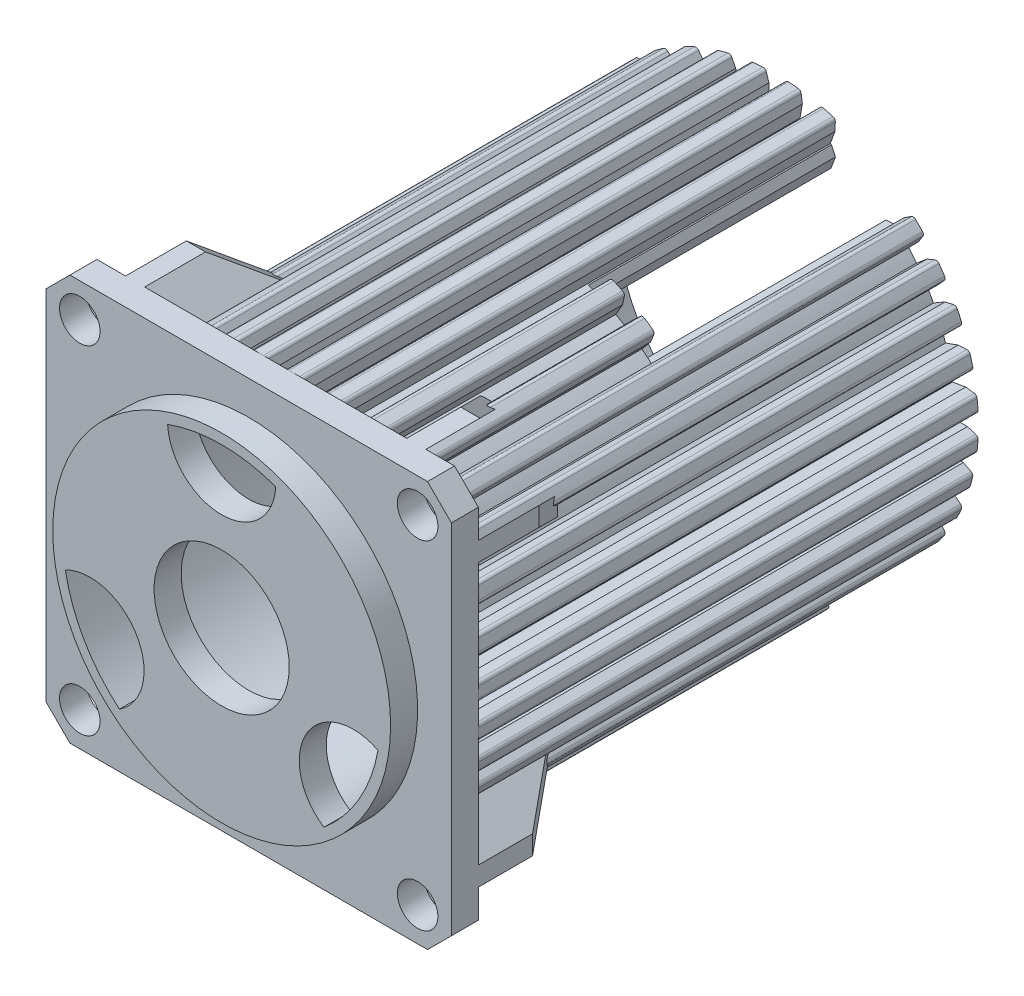
SolidWorks part; units mm, degrees
ref_plane "Alzado" through (0, 0, 0) normal (0, 0, 1) x (1, 0, 0)
ref_plane "Planta" through (0, 0, 0) normal (0, 1, 0) x (1, 0, 0)
ref_plane "Vista lateral" through (0, 0, 0) normal (1, 0, 0) x (0, 0, -1)
sketch "Croquis1" plane through (0, 0, 0) normal (0, 0, 1) x (1, 0, 0)
  line L1 (-15, -15) -> (15, -15)
  line L2 (-15, -15) -> (-15, 15)
  line L3 (-15, 15) -> (15, 15)
  line L4 (15, -15) -> (15, 15)
  line L5 (-15, -15) -> (15, 15) construction
  line L6 (-15, 15) -> (15, -15) construction
  circle A0 centre (0, 0) radius 11.75
  circle A1 centre (-12.5, 12.5) radius 1.5
  circle A2 centre (-12.5, -12.5) radius 1.5
  circle A3 centre (12.5, -12.5) radius 1.5
  circle A4 centre (12.5, 12.5) radius 1.5
  dimension "D1" = 23.5
  dimension "D3" = 3
  dimension "D4" = 25
  dimension "D2" = 30
extrude "Saliente-Extruir1" add sketch "Croquis1" against normal blind 2
sketch "Croquis2" plane through (0, 0, 0) normal (0, 0, 1) x (1, 0, 0)
  line L0 (-15, -15) -> (15, 15) construction
  circle A0 centre (0, 0) radius 12.5
  circle A1 centre (0, 0) radius 11.75
  circle A2 centre (0, 0) radius 11.75 construction
  dimension "D1" = 25
extrude "Saliente-Extruir2" add sketch "Croquis2" along normal blind 2
sketch "Croquis3" plane through (0, 0, 2) normal (0, 0, 1) x (1, 0, 0)
  line L0 (0, 11.75) -> (0, 7.25) construction
  circle A1 centre (0, 0) radius 11.75
  arc A2 (-4, 11.0482) -> (4, 11.0482) centre (0, 0) cw construction
  arc A3 (-4, 11.0482) -> (4, 11.0482) centre (0, 11.2554) ccw
  arc A4 (11.568, -2.06) -> (7.568, -8.9882) centre (9.7474, -5.6277) ccw
  arc A5 (11.568, -2.06) -> (7.568, -8.9882) centre (0, 0) cw construction
  arc A6 (-7.568, -8.9882) -> (-11.568, -2.06) centre (-9.7474, -5.6277) ccw
  arc A7 (-7.568, -8.9882) -> (-11.568, -2.06) centre (0, 0) cw construction
  circle A8 centre (0, 0) radius 5
  point P16 (0, 0)
  dimension "D5" = 10
  dimension "D1" = 8
  dimension "D3" = 4.5
  dimension "D2" = 4
  dimension "D4" = 3
extrude "Saliente-Extruir3" add sketch "Croquis3" against normal blind 2 contours A6 A1 A4 A3 region at (11.3783, -1.0052, 2)
chamfer "Chaflán2" distance 1.7678 angle 45 4 edges at (-15, -15, -1) (-15, 15, -1) (15, -15, -1) (15, 15, -1)
sketch "Croquis4" plane through (0, 0, -2) normal (0, 0, -1) x (-1, 0, 0)
  line L0 (-0.5, 13.1907) -> (-0.5, 14.1907)
  line L1 (-0.5, 14.1907) -> (-0.6914, 14.796)
  line L2 (0.5, 13.1907) -> (0.5, 14.1907)
  line L3 (0.5, 14.1907) -> (0.6914, 14.796)
  line L4 (0, 13.2002) -> (0, 11.75) construction
  line L5 (0, 13.2002) -> (0, 15) construction
  line L8 (1.9718, 14.062) -> (1.8884, 14.6913)
  line L9 (1.7981, 13.0772) -> (1.9718, 14.062)
  line L10 (2.783, 12.9035) -> (2.9566, 13.8883)
  line L11 (2.9566, 13.8883) -> (3.2502, 14.4512)
  line L12 (4.3837, 13.5059) -> (4.4108, 14.1402)
  line L13 (4.0417, 12.5662) -> (4.3837, 13.5059)
  line L14 (4.9813, 12.2242) -> (5.3234, 13.1639)
  line L15 (5.3234, 13.1639) -> (5.7103, 13.6673)
  line L16 (6.6624, 12.5395) -> (6.7992, 13.1595)
  line L17 (6.1624, 11.6735) -> (6.6624, 12.5395)
  line L18 (7.0284, 11.1735) -> (7.5284, 12.0395)
  line L19 (7.5284, 12.0395) -> (7.9968, 12.468)
  line L20 (8.7386, 11.1921) -> (8.981, 11.7789)
  line L21 (8.0958, 10.4261) -> (8.7386, 11.1921)
  line L22 (8.8619, 9.7833) -> (9.5047, 10.5493)
  line L23 (9.5047, 10.5493) -> (10.0404, 10.89)
  line L24 (10.5493, 9.5047) -> (10.89, 10.0404)
  line L25 (9.7833, 8.8619) -> (10.5493, 9.5047)
  line L26 (10.4261, 8.0958) -> (11.1921, 8.7386)
  line L27 (11.1921, 8.7386) -> (11.7789, 8.981)
  line L28 (12.0395, 7.5284) -> (12.468, 7.9968)
  line L29 (11.1735, 7.0284) -> (12.0395, 7.5284)
  line L30 (11.6735, 6.1624) -> (12.5395, 6.6624)
  line L31 (12.5395, 6.6624) -> (13.1595, 6.7992)
  line L32 (13.1639, 5.3234) -> (13.6673, 5.7103)
  line L33 (12.2242, 4.9813) -> (13.1639, 5.3234)
  line L34 (12.5662, 4.0417) -> (13.5059, 4.3837)
  line L35 (13.5059, 4.3837) -> (14.1402, 4.4108)
  line L36 (13.8883, 2.9566) -> (14.4512, 3.2502)
  line L37 (12.9035, 2.783) -> (13.8883, 2.9566)
  line L38 (13.0772, 1.7981) -> (14.062, 1.9718)
  line L39 (14.062, 1.9718) -> (14.6913, 1.8884)
  line L40 (14.1907, 0.5) -> (14.796, 0.6914)
  line L41 (13.1907, 0.5) -> (14.1907, 0.5)
  line L42 (13.1907, -0.5) -> (14.1907, -0.5)
  line L43 (14.1907, -0.5) -> (14.796, -0.6914)
  line L44 (14.062, -1.9718) -> (14.6913, -1.8884)
  line L45 (13.0772, -1.7981) -> (14.062, -1.9718)
  line L46 (12.9035, -2.783) -> (13.8883, -2.9566)
  line L47 (13.8883, -2.9566) -> (14.4512, -3.2502)
  line L48 (13.5059, -4.3837) -> (14.1402, -4.4108)
  line L49 (12.5662, -4.0417) -> (13.5059, -4.3837)
  line L50 (12.2242, -4.9813) -> (13.1639, -5.3234)
  line L51 (13.1639, -5.3234) -> (13.6673, -5.7103)
  line L52 (12.5395, -6.6624) -> (13.1595, -6.7992)
  line L53 (11.6735, -6.1624) -> (12.5395, -6.6624)
  line L54 (11.1735, -7.0284) -> (12.0395, -7.5284)
  line L55 (12.0395, -7.5284) -> (12.468, -7.9968)
  line L56 (11.1921, -8.7386) -> (11.7789, -8.981)
  line L57 (10.4261, -8.0958) -> (11.1921, -8.7386)
  line L58 (9.7833, -8.8619) -> (10.5493, -9.5047)
  line L59 (10.5493, -9.5047) -> (10.89, -10.0404)
  line L60 (9.5047, -10.5493) -> (10.0404, -10.89)
  line L61 (8.8619, -9.7833) -> (9.5047, -10.5493)
  line L62 (8.0958, -10.4261) -> (8.7386, -11.1921)
  line L63 (8.7386, -11.1921) -> (8.981, -11.7789)
  line L64 (7.5284, -12.0395) -> (7.9968, -12.468)
  line L65 (7.0284, -11.1735) -> (7.5284, -12.0395)
  line L66 (6.1624, -11.6735) -> (6.6624, -12.5395)
  line L67 (6.6624, -12.5395) -> (6.7992, -13.1595)
  line L68 (5.3234, -13.1639) -> (5.7103, -13.6673)
  line L69 (4.9813, -12.2242) -> (5.3234, -13.1639)
  line L70 (4.0417, -12.5662) -> (4.3837, -13.5059)
  line L71 (4.3837, -13.5059) -> (4.4108, -14.1402)
  line L72 (2.9566, -13.8883) -> (3.2502, -14.4512)
  line L73 (2.783, -12.9035) -> (2.9566, -13.8883)
  line L74 (1.7981, -13.0772) -> (1.9718, -14.062)
  line L75 (1.9718, -14.062) -> (1.8884, -14.6913)
  line L76 (0.5, -14.1907) -> (0.6914, -14.796)
  line L77 (0.5, -13.1907) -> (0.5, -14.1907)
  line L78 (-0.5, -13.1907) -> (-0.5, -14.1907)
  line L79 (-0.5, -14.1907) -> (-0.6914, -14.796)
  line L80 (-1.9718, -14.062) -> (-1.8884, -14.6913)
  line L81 (-1.7981, -13.0772) -> (-1.9718, -14.062)
  line L82 (-2.783, -12.9035) -> (-2.9566, -13.8883)
  line L83 (-2.9566, -13.8883) -> (-3.2502, -14.4512)
  line L84 (-4.3837, -13.5059) -> (-4.4108, -14.1402)
  line L85 (-4.0417, -12.5662) -> (-4.3837, -13.5059)
  line L86 (-4.9813, -12.2242) -> (-5.3234, -13.1639)
  line L87 (-5.3234, -13.1639) -> (-5.7103, -13.6673)
  line L88 (-6.6624, -12.5395) -> (-6.7992, -13.1595)
  line L89 (-6.1624, -11.6735) -> (-6.6624, -12.5395)
  line L90 (-7.0284, -11.1735) -> (-7.5284, -12.0395)
  line L91 (-7.5284, -12.0395) -> (-7.9968, -12.468)
  line L92 (-8.7386, -11.1921) -> (-8.981, -11.7789)
  line L93 (-8.0958, -10.4261) -> (-8.7386, -11.1921)
  line L94 (-8.8619, -9.7833) -> (-9.5047, -10.5493)
  line L95 (-9.5047, -10.5493) -> (-10.0404, -10.89)
  line L96 (-10.5493, -9.5047) -> (-10.89, -10.0404)
  line L97 (-9.7833, -8.8619) -> (-10.5493, -9.5047)
  line L98 (-10.4261, -8.0958) -> (-11.1921, -8.7386)
  line L99 (-11.1921, -8.7386) -> (-11.7789, -8.981)
  line L100 (-12.0395, -7.5284) -> (-12.468, -7.9968)
  line L101 (-11.1735, -7.0284) -> (-12.0395, -7.5284)
  line L102 (-11.6735, -6.1624) -> (-12.5395, -6.6624)
  line L103 (-12.5395, -6.6624) -> (-13.1595, -6.7992)
  line L104 (-13.1639, -5.3234) -> (-13.6673, -5.7103)
  line L105 (-12.2242, -4.9813) -> (-13.1639, -5.3234)
  line L106 (-12.5662, -4.0417) -> (-13.5059, -4.3837)
  line L107 (-13.5059, -4.3837) -> (-14.1402, -4.4108)
  line L108 (-13.8883, -2.9566) -> (-14.4512, -3.2502)
  line L109 (-12.9035, -2.783) -> (-13.8883, -2.9566)
  line L110 (-13.0772, -1.7981) -> (-14.062, -1.9718)
  line L111 (-14.062, -1.9718) -> (-14.6913, -1.8884)
  line L112 (-14.1907, -0.5) -> (-14.796, -0.6914)
  line L113 (-13.1907, -0.5) -> (-14.1907, -0.5)
  line L114 (-13.1907, 0.5) -> (-14.1907, 0.5)
  line L115 (-14.1907, 0.5) -> (-14.796, 0.6914)
  line L116 (-14.062, 1.9718) -> (-14.6913, 1.8884)
  line L117 (-13.0772, 1.7981) -> (-14.062, 1.9718)
  line L118 (-12.9035, 2.783) -> (-13.8883, 2.9566)
  line L119 (-13.8883, 2.9566) -> (-14.4512, 3.2502)
  line L120 (-13.5059, 4.3837) -> (-14.1402, 4.4108)
  line L121 (-12.5662, 4.0417) -> (-13.5059, 4.3837)
  line L122 (-12.2242, 4.9813) -> (-13.1639, 5.3234)
  line L123 (-13.1639, 5.3234) -> (-13.6673, 5.7103)
  line L124 (-12.5395, 6.6624) -> (-13.1595, 6.7992)
  line L125 (-11.6735, 6.1624) -> (-12.5395, 6.6624)
  line L126 (-11.1735, 7.0284) -> (-12.0395, 7.5284)
  line L127 (-12.0395, 7.5284) -> (-12.468, 7.9968)
  line L128 (-11.1921, 8.7386) -> (-11.7789, 8.981)
  line L129 (-10.4261, 8.0958) -> (-11.1921, 8.7386)
  line L130 (-9.7833, 8.8619) -> (-10.5493, 9.5047)
  line L131 (-10.5493, 9.5047) -> (-10.89, 10.0404)
  line L132 (-9.5047, 10.5493) -> (-10.0404, 10.89)
  line L133 (-8.8619, 9.7833) -> (-9.5047, 10.5493)
  line L134 (-8.0958, 10.4261) -> (-8.7386, 11.1921)
  line L135 (-8.7386, 11.1921) -> (-8.981, 11.7789)
  line L136 (-7.5284, 12.0395) -> (-7.9968, 12.468)
  line L137 (-7.0284, 11.1735) -> (-7.5284, 12.0395)
  line L138 (-6.1624, 11.6735) -> (-6.6624, 12.5395)
  line L139 (-6.6624, 12.5395) -> (-6.7992, 13.1595)
  line L140 (-5.3234, 13.1639) -> (-5.7103, 13.6673)
  line L141 (-4.9813, 12.2242) -> (-5.3234, 13.1639)
  line L142 (-4.0417, 12.5662) -> (-4.3837, 13.5059)
  line L143 (-4.3837, 13.5059) -> (-4.4108, 14.1402)
  line L144 (-2.9566, 13.8883) -> (-3.2502, 14.4512)
  line L145 (-2.783, 12.9035) -> (-2.9566, 13.8883)
  line L146 (-1.7981, 13.0772) -> (-1.9718, 14.062)
  line L147 (-1.9718, 14.062) -> (-1.8884, 14.6913)
  arc A2 (-0.5, 13.1907) -> (0.5, 13.1907) centre (0, 0) cw
  circle A3 centre (0, 0) radius 15 construction
  arc A6 (-0.6914, 14.796) -> (-0.9456, 14.9702) centre (-0.9298, 14.7207) ccw
  arc A7 (0.6914, 14.796) -> (0.9456, 14.9702) centre (0.9298, 14.7207) cw
  arc A8 (1.8884, 14.6913) -> (1.6684, 14.9069) centre (1.6405, 14.6585) ccw
  arc A9 (1.7981, 13.0772) -> (2.783, 12.9035) centre (0, 0) cw
  arc A10 (3.2502, 14.4512) -> (3.5307, 14.5785) centre (3.4719, 14.3356) cw
  arc A11 (4.4108, 14.1402) -> (4.2316, 14.3908) centre (4.161, 14.1509) ccw
  arc A12 (4.0417, 12.5662) -> (4.9813, 12.2242) centre (0, 0) cw
  arc A13 (5.7103, 13.6673) -> (6.0086, 13.744) centre (5.9085, 13.5149) cw
  arc A14 (6.7992, 13.1595) -> (6.6662, 13.4373) centre (6.5551, 13.2134) ccw
  arc A15 (6.1624, 11.6735) -> (7.0284, 11.1735) centre (0, 0) cw
  arc A16 (7.9968, 12.468) -> (8.304, 12.4918) centre (8.1656, 12.2836) cw
  arc A17 (8.981, 11.7789) -> (8.8983, 12.0756) centre (8.75, 11.8743) ccw
  arc A18 (8.0958, 10.4261) -> (8.8619, 9.7833) centre (0, 0) cw
  arc A19 (10.0404, 10.89) -> (10.347, 10.86) centre (10.1745, 10.679) cw
  arc A20 (10.89, 10.0404) -> (10.86, 10.347) centre (10.679, 10.1745) ccw
  arc A21 (9.7833, 8.8619) -> (10.4261, 8.0958) centre (0, 0) cw
  arc A22 (11.7789, 8.981) -> (12.0756, 8.8983) centre (11.8743, 8.75) cw
  arc A23 (12.468, 7.9968) -> (12.4918, 8.304) centre (12.2836, 8.1656) ccw
  arc A24 (11.1735, 7.0284) -> (11.6735, 6.1624) centre (0, 0) cw
  arc A25 (13.1595, 6.7992) -> (13.4373, 6.6662) centre (13.2134, 6.5551) cw
  arc A26 (13.6673, 5.7103) -> (13.744, 6.0086) centre (13.5149, 5.9085) ccw
  arc A27 (12.2242, 4.9813) -> (12.5662, 4.0417) centre (0, 0) cw
  arc A28 (14.1402, 4.4108) -> (14.3908, 4.2316) centre (14.1509, 4.161) cw
  arc A29 (14.4512, 3.2502) -> (14.5785, 3.5307) centre (14.3356, 3.4719) ccw
  arc A30 (12.9035, 2.783) -> (13.0772, 1.7981) centre (0, 0) cw
  arc A31 (14.6913, 1.8884) -> (14.9069, 1.6684) centre (14.6585, 1.6405) cw
  arc A32 (14.796, 0.6914) -> (14.9702, 0.9456) centre (14.7207, 0.9298) ccw
  arc A33 (13.1907, 0.5) -> (13.1907, -0.5) centre (0, 0) cw
  arc A34 (14.796, -0.6914) -> (14.9702, -0.9456) centre (14.7207, -0.9298) cw
  arc A35 (14.6913, -1.8884) -> (14.9069, -1.6684) centre (14.6585, -1.6405) ccw
  arc A36 (13.0772, -1.7981) -> (12.9035, -2.783) centre (0, 0) cw
  arc A37 (14.4512, -3.2502) -> (14.5785, -3.5307) centre (14.3356, -3.4719) cw
  arc A38 (14.1402, -4.4108) -> (14.3908, -4.2316) centre (14.1509, -4.161) ccw
  arc A39 (12.5662, -4.0417) -> (12.2242, -4.9813) centre (0, 0) cw
  arc A40 (13.6673, -5.7103) -> (13.744, -6.0086) centre (13.5149, -5.9085) cw
  arc A41 (13.1595, -6.7992) -> (13.4373, -6.6662) centre (13.2134, -6.5551) ccw
  arc A42 (11.6735, -6.1624) -> (11.1735, -7.0284) centre (0, 0) cw
  arc A43 (12.468, -7.9968) -> (12.4918, -8.304) centre (12.2836, -8.1656) cw
  arc A44 (11.7789, -8.981) -> (12.0756, -8.8983) centre (11.8743, -8.75) ccw
  arc A45 (10.4261, -8.0958) -> (9.7833, -8.8619) centre (0, 0) cw
  arc A46 (10.89, -10.0404) -> (10.86, -10.347) centre (10.679, -10.1745) cw
  arc A47 (10.0404, -10.89) -> (10.347, -10.86) centre (10.1745, -10.679) ccw
  arc A48 (8.8619, -9.7833) -> (8.0958, -10.4261) centre (0, 0) cw
  arc A49 (8.981, -11.7789) -> (8.8983, -12.0756) centre (8.75, -11.8743) cw
  arc A50 (7.9968, -12.468) -> (8.304, -12.4918) centre (8.1656, -12.2836) ccw
  arc A51 (7.0284, -11.1735) -> (6.1624, -11.6735) centre (0, 0) cw
  arc A52 (6.7992, -13.1595) -> (6.6662, -13.4373) centre (6.5551, -13.2134) cw
  arc A53 (5.7103, -13.6673) -> (6.0086, -13.744) centre (5.9085, -13.5149) ccw
  arc A54 (4.9813, -12.2242) -> (4.0417, -12.5662) centre (0, 0) cw
  arc A55 (4.4108, -14.1402) -> (4.2316, -14.3908) centre (4.161, -14.1509) cw
  arc A56 (3.2502, -14.4512) -> (3.5307, -14.5785) centre (3.4719, -14.3356) ccw
  arc A57 (2.783, -12.9035) -> (1.7981, -13.0772) centre (0, 0) cw
  arc A58 (1.8884, -14.6913) -> (1.6684, -14.9069) centre (1.6405, -14.6585) cw
  arc A59 (0.6914, -14.796) -> (0.9456, -14.9702) centre (0.9298, -14.7207) ccw
  arc A60 (0.5, -13.1907) -> (-0.5, -13.1907) centre (0, 0) cw
  arc A61 (-0.6914, -14.796) -> (-0.9456, -14.9702) centre (-0.9298, -14.7207) cw
  arc A62 (-1.8884, -14.6913) -> (-1.6684, -14.9069) centre (-1.6405, -14.6585) ccw
  arc A63 (-1.7981, -13.0772) -> (-2.783, -12.9035) centre (0, 0) cw
  arc A64 (-3.2502, -14.4512) -> (-3.5307, -14.5785) centre (-3.4719, -14.3356) cw
  arc A65 (-4.4108, -14.1402) -> (-4.2316, -14.3908) centre (-4.161, -14.1509) ccw
  arc A66 (-4.0417, -12.5662) -> (-4.9813, -12.2242) centre (0, 0) cw
  arc A67 (-5.7103, -13.6673) -> (-6.0086, -13.744) centre (-5.9085, -13.5149) cw
  arc A68 (-6.7992, -13.1595) -> (-6.6662, -13.4373) centre (-6.5551, -13.2134) ccw
  arc A69 (-6.1624, -11.6735) -> (-7.0284, -11.1735) centre (0, 0) cw
  arc A70 (-7.9968, -12.468) -> (-8.304, -12.4918) centre (-8.1656, -12.2836) cw
  arc A71 (-8.981, -11.7789) -> (-8.8983, -12.0756) centre (-8.75, -11.8743) ccw
  arc A72 (-8.0958, -10.4261) -> (-8.8619, -9.7833) centre (0, 0) cw
  arc A73 (-10.0404, -10.89) -> (-10.347, -10.86) centre (-10.1745, -10.679) cw
  arc A74 (-10.89, -10.0404) -> (-10.86, -10.347) centre (-10.679, -10.1745) ccw
  arc A75 (-9.7833, -8.8619) -> (-10.4261, -8.0958) centre (0, 0) cw
  arc A76 (-11.7789, -8.981) -> (-12.0756, -8.8983) centre (-11.8743, -8.75) cw
  arc A77 (-12.468, -7.9968) -> (-12.4918, -8.304) centre (-12.2836, -8.1656) ccw
  arc A78 (-11.1735, -7.0284) -> (-11.6735, -6.1624) centre (0, 0) cw
  arc A79 (-13.1595, -6.7992) -> (-13.4373, -6.6662) centre (-13.2134, -6.5551) cw
  arc A80 (-13.6673, -5.7103) -> (-13.744, -6.0086) centre (-13.5149, -5.9085) ccw
  arc A81 (-12.2242, -4.9813) -> (-12.5662, -4.0417) centre (0, 0) cw
  arc A82 (-14.1402, -4.4108) -> (-14.3908, -4.2316) centre (-14.1509, -4.161) cw
  arc A83 (-14.4512, -3.2502) -> (-14.5785, -3.5307) centre (-14.3356, -3.4719) ccw
  arc A84 (-12.9035, -2.783) -> (-13.0772, -1.7981) centre (0, 0) cw
  arc A85 (-14.6913, -1.8884) -> (-14.9069, -1.6684) centre (-14.6585, -1.6405) cw
  arc A86 (-14.796, -0.6914) -> (-14.9702, -0.9456) centre (-14.7207, -0.9298) ccw
  arc A87 (-13.1907, -0.5) -> (-13.1907, 0.5) centre (0, 0) cw
  arc A88 (-14.796, 0.6914) -> (-14.9702, 0.9456) centre (-14.7207, 0.9298) cw
  arc A89 (-14.6913, 1.8884) -> (-14.9069, 1.6684) centre (-14.6585, 1.6405) ccw
  arc A90 (-13.0772, 1.7981) -> (-12.9035, 2.783) centre (0, 0) cw
  arc A91 (-14.4512, 3.2502) -> (-14.5785, 3.5307) centre (-14.3356, 3.4719) cw
  arc A92 (-14.1402, 4.4108) -> (-14.3908, 4.2316) centre (-14.1509, 4.161) ccw
  arc A93 (-12.5662, 4.0417) -> (-12.2242, 4.9813) centre (0, 0) cw
  arc A94 (-13.6673, 5.7103) -> (-13.744, 6.0086) centre (-13.5149, 5.9085) cw
  arc A95 (-13.1595, 6.7992) -> (-13.4373, 6.6662) centre (-13.2134, 6.5551) ccw
  arc A96 (-11.6735, 6.1624) -> (-11.1735, 7.0284) centre (0, 0) cw
  arc A97 (-12.468, 7.9968) -> (-12.4918, 8.304) centre (-12.2836, 8.1656) cw
  arc A98 (-11.7789, 8.981) -> (-12.0756, 8.8983) centre (-11.8743, 8.75) ccw
  arc A99 (-10.4261, 8.0958) -> (-9.7833, 8.8619) centre (0, 0) cw
  arc A100 (-10.89, 10.0404) -> (-10.86, 10.347) centre (-10.679, 10.1745) cw
  arc A101 (-10.0404, 10.89) -> (-10.347, 10.86) centre (-10.1745, 10.679) ccw
  arc A102 (-8.8619, 9.7833) -> (-8.0958, 10.4261) centre (0, 0) cw
  arc A103 (-8.981, 11.7789) -> (-8.8983, 12.0756) centre (-8.75, 11.8743) cw
  arc A104 (-7.9968, 12.468) -> (-8.304, 12.4918) centre (-8.1656, 12.2836) ccw
  arc A105 (-7.0284, 11.1735) -> (-6.1624, 11.6735) centre (0, 0) cw
  arc A106 (-6.7992, 13.1595) -> (-6.6662, 13.4373) centre (-6.5551, 13.2134) cw
  arc A107 (-5.7103, 13.6673) -> (-6.0086, 13.744) centre (-5.9085, 13.5149) ccw
  arc A108 (-4.9813, 12.2242) -> (-4.0417, 12.5662) centre (0, 0) cw
  arc A109 (-4.4108, 14.1402) -> (-4.2316, 14.3908) centre (-4.161, 14.1509) cw
  arc A110 (-3.2502, 14.4512) -> (-3.5307, 14.5785) centre (-3.4719, 14.3356) ccw
  arc A111 (-2.783, 12.9035) -> (-1.7981, 13.0772) centre (0, 0) cw
  arc A112 (-1.8884, 14.6913) -> (-1.6684, 14.9069) centre (-1.6405, 14.6585) cw
  arc A113 (-0.9456, 14.9702) -> (-1.6684, 14.9069) centre (0, 0) ccw
  arc A114 (1.6684, 14.9069) -> (0.9456, 14.9702) centre (0, 0) ccw
  arc A115 (4.2316, 14.3908) -> (3.5307, 14.5785) centre (0, 0) ccw
  arc A116 (6.6662, 13.4373) -> (6.0086, 13.744) centre (0, 0) ccw
  arc A117 (8.8983, 12.0756) -> (8.304, 12.4918) centre (0, 0) ccw
  arc A118 (10.86, 10.347) -> (10.347, 10.86) centre (0, 0) ccw
  arc A119 (12.4918, 8.304) -> (12.0756, 8.8983) centre (0, 0) ccw
  arc A120 (13.744, 6.0086) -> (13.4373, 6.6662) centre (0, 0) ccw
  arc A121 (14.5785, 3.5307) -> (14.3908, 4.2316) centre (0, 0) ccw
  arc A122 (14.9702, 0.9456) -> (14.9069, 1.6684) centre (0, 0) ccw
  arc A123 (14.9069, -1.6684) -> (14.9702, -0.9456) centre (0, 0) ccw
  arc A124 (14.3908, -4.2316) -> (14.5785, -3.5307) centre (0, 0) ccw
  arc A125 (13.4373, -6.6662) -> (13.744, -6.0086) centre (0, 0) ccw
  arc A126 (12.0756, -8.8983) -> (12.4918, -8.304) centre (0, 0) ccw
  arc A127 (10.347, -10.86) -> (10.86, -10.347) centre (0, 0) ccw
  arc A128 (8.304, -12.4918) -> (8.8983, -12.0756) centre (0, 0) ccw
  arc A129 (6.0086, -13.744) -> (6.6662, -13.4373) centre (0, 0) ccw
  arc A130 (3.5307, -14.5785) -> (4.2316, -14.3908) centre (0, 0) ccw
  arc A131 (0.9456, -14.9702) -> (1.6684, -14.9069) centre (0, 0) ccw
  arc A132 (-1.6684, -14.9069) -> (-0.9456, -14.9702) centre (0, 0) ccw
  arc A133 (-4.2316, -14.3908) -> (-3.5307, -14.5785) centre (0, 0) ccw
  arc A134 (-6.6662, -13.4373) -> (-6.0086, -13.744) centre (0, 0) ccw
  arc A135 (-8.8983, -12.0756) -> (-8.304, -12.4918) centre (0, 0) ccw
  arc A136 (-10.86, -10.347) -> (-10.347, -10.86) centre (0, 0) ccw
  arc A137 (-12.4918, -8.304) -> (-12.0756, -8.8983) centre (0, 0) ccw
  arc A138 (-13.744, -6.0086) -> (-13.4373, -6.6662) centre (0, 0) ccw
  arc A139 (-14.5785, -3.5307) -> (-14.3908, -4.2316) centre (0, 0) ccw
  arc A140 (-14.9702, -0.9456) -> (-14.9069, -1.6684) centre (0, 0) ccw
  arc A141 (-14.9069, 1.6684) -> (-14.9702, 0.9456) centre (0, 0) ccw
  arc A142 (-14.3908, 4.2316) -> (-14.5785, 3.5307) centre (0, 0) ccw
  arc A143 (-13.4373, 6.6662) -> (-13.744, 6.0086) centre (0, 0) ccw
  arc A144 (-12.0756, 8.8983) -> (-12.4918, 8.304) centre (0, 0) ccw
  arc A145 (-10.347, 10.86) -> (-10.86, 10.347) centre (0, 0) ccw
  arc A146 (-8.304, 12.4918) -> (-8.8983, 12.0756) centre (0, 0) ccw
  arc A147 (-6.0086, 13.744) -> (-6.6662, 13.4373) centre (0, 0) ccw
  arc A148 (-3.5307, 14.5785) -> (-4.2316, 14.3908) centre (0, 0) ccw
  circle A149 centre (0, 0) radius 11.75 construction
  circle A152 centre (0, 0) radius 11.75
  point P12 (0, 13.2002)
  point P370 (0, 0)
  point P443 (0, 0)
  dimension "D1" = 30
  dimension "D3" = 1
  dimension "D9" = 0.25
  dimension "D4" = 1.8911
  dimension "D5" = 1.3829
  dimension "D7" = 1
  dimension "D8" = 36
  dimension "D10" = 36
extrude "Saliente-Extruir5" add sketch "Croquis4" along normal blind 37 contours A110 A148 A109 L143 L142 A108 L141 L140 A107 A147 A106 L139 L138 A105 L137 L136 A104 A146 A103 L135 L134 A102 L133 L132 A101 A145 A100 L131 L130 A99 L129 L128 A98 A144 A97 L127 L126 A96 L125 L124 A95 A143 A94 L123 L122 A93 L121 L120 A92 A142 A91 region at (0, 12.7768, -2)
sketch "Croquis5" plane through (0, 0, -39) normal (0, 0, -1) x (-1, 0, 0)
  line L0 (-8.1574, 9.7217) -> (-7.5528, 9.001)
  line L1 (-8.8619, 9.7833) -> (-8.1574, 9.7217)
  line L2 (0, 0) -> (-7.5528, 9.001) construction
  line L3 (-5.9105, 10.1552) -> (0, 0) construction
  line L4 (-4.1292, 12.5378) -> (-4.4236, 11.8948)
  line L5 (-4.4236, 11.8948) -> (-4.0956, 11.0131)
  line L7 (-10.7669, 12.0536) -> (-5.1428, 15.3227)
  line L9 (-8.8619, 9.7833) -> (-10.7669, 12.0536)
  line L10 (-8.8619, 9.7833) -> (-9.5047, 10.5493) construction
  line L11 (-4.1292, 12.5378) -> (-5.1428, 15.3227)
  line L12 (0, 0) -> (-11.75, 0) construction
  line L13 (-4.0417, 12.5662) -> (-4.3837, 13.5059) construction
  line L14 (-8.8619, -9.7833) -> (-10.7669, -12.0536)
  line L15 (-8.8619, -9.7833) -> (-8.1574, -9.7217)
  line L16 (-8.1574, -9.7217) -> (-7.5528, -9.001)
  line L17 (-4.4236, -11.8948) -> (-4.0956, -11.0131)
  line L18 (-4.1292, -12.5378) -> (-4.4236, -11.8948)
  line L19 (-4.1292, -12.5378) -> (-5.1428, -15.3227)
  line L20 (-10.7669, -12.0536) -> (-5.1428, -15.3227)
  line L22 (15.4801, -2.7296) -> (15.4801, 2.7296)
  line L24 (12.9997, -2.2923) -> (12.7074, -2)
  line L25 (11.75, 0) -> (15, 0) construction
  line L26 (12.7074, -2) -> (11.5785, -2)
  line L27 (15, 13.2322) -> (15, -13.2322) construction
  line L28 (12.9997, -2.2923) -> (15.4801, -2.7296)
  line L29 (12.9035, -2.783) -> (13.8883, -2.9566) construction
  line L30 (12.7074, 2) -> (11.5785, 2)
  line L31 (12.9997, 2.2923) -> (12.7074, 2)
  line L32 (12.9997, 2.2923) -> (15.4801, 2.7296)
  arc A0 (-7.5528, 9.001) -> (-4.0956, 11.0131) centre (0, 0) cw
  arc A1 (-4, 11.0482) -> (-11.568, -2.06) centre (0, 0) ccw construction
  circle A2 centre (0, 0) radius 11.75 construction
  arc A3 (-7.5528, -9.001) -> (-4.0956, -11.0131) centre (0, 0) ccw
  arc A4 (11.5785, -2) -> (11.5785, 2) centre (0, 0) ccw
  arc A5 (11.568, -2.06) -> (4, 11.0482) centre (0, 0) ccw construction
  arc A6 (12.9035, -2.783) -> (13.0772, -1.7981) centre (0, 0) ccw construction
  point P34 (11.75, 0)
  dimension "D1" = 45
  dimension "D2" = 0.5
  dimension "D3" = 4
  dimension "D4" = 4
  dimension "D5" = 45
  dimension "D6" = 0.5
extrude "Cortar-Extruir2" cut sketch "Croquis5" against normal blind 18
sketch "Croquis6" plane through (0, 0, -39) normal (0, 0, -1) x (-1, 0, 0)
  line L0 (2.783, -12.9035) -> (2.2445, -12.5179)
  line L1 (2.2445, -12.5179) -> (2.0764, -11.5651)
  line L2 (2.783, -12.9035) -> (2.9566, -13.8883) construction
  line L3 (2.783, -12.9035) -> (3.5728, -17.383)
  line L4 (-8.7714, -7.8182) -> (-9.6175, -8.5282)
  line L5 (-9.6175, -8.5282) -> (-10.1119, -8.4849)
  line L6 (-9.7833, -8.8619) -> (-10.5493, -9.5047) construction
  line L7 (-10.1119, -8.4849) -> (-13.5963, -11.4087)
  line L8 (-13.5963, -11.4087) -> (3.5728, -17.383)
  arc A0 (2.0764, -11.5651) -> (-8.7714, -7.8182) centre (0, 0) cw
  arc A1 (-7.568, -8.9882) -> (7.568, -8.9882) centre (0, 0) ccw construction
  arc A2 (-7.5528, 9.001) -> (-7.5528, -9.001) centre (0, 0) ccw construction
  arc A3 (1.7981, -13.0772) -> (2.783, -12.9035) centre (0, 0) ccw construction
  arc A4 (-10.4261, -8.0958) -> (-9.7833, -8.8619) centre (0, 0) ccw construction
  dimension "D1" = 2
  dimension "D2" = 6.5
  dimension "D3" = 45
extrude "Cortar-Extruir3" cut sketch "Croquis6" against normal blind 7
sketch "Croquis7" plane through (0, 0, -2) normal (0, 0, -1) x (-1, 0, 0)
  line L0 (-15, 11.1102) -> (-11.0737, 7.1846)
  line L1 (-15, -13.2322) -> (-15, 13.2322) construction
  line L2 (-11.1117, 15) -> (-7.1846, 11.0737)
  line L3 (-13.2322, 15) -> (-15, 13.2322) construction
  line L4 (-13.2322, 15) -> (13.2322, 15) construction
  line L6 (-11.0737, 7.1846) -> (-7.1846, 11.0737) construction
  line L7 (-15, 11.1102) -> (-15, 9.6961)
  line L8 (-11.601, 6.2978) -> (-15, 9.6961)
  line L9 (-15, 9.6961) -> (-15, 11.1102)
  line L10 (-9.6973, 15) -> (-6.2977, 11.601)
  line L11 (0, 0) -> (-15, 0) construction
  line L12 (0, 0) -> (0, 15) construction
  line L13 (-11.1117, 15) -> (-9.6973, 15)
  line L14 (-11.1117, -15) -> (-9.6973, -15)
  line L15 (-9.6973, -15) -> (-6.2977, -11.601)
  line L16 (-11.1117, -15) -> (-7.1846, -11.0737)
  line L17 (-15, -11.1102) -> (-11.0737, -7.1846)
  line L18 (-11.601, -6.2978) -> (-15, -9.6961)
  line L19 (-15, -11.1102) -> (-15, -9.6961)
  line L20 (9.6973, 15) -> (6.2977, 11.601)
  line L21 (11.1117, 15) -> (7.1846, 11.0737)
  line L22 (11.1117, 15) -> (9.6973, 15)
  line L23 (15, 11.1102) -> (15, 9.6961)
  line L24 (15, 11.1102) -> (11.0737, 7.1846)
  line L25 (11.601, 6.2978) -> (15, 9.6961)
  line L26 (11.601, -6.2978) -> (15, -9.6961)
  line L27 (15, -11.1102) -> (15, -9.6961)
  line L28 (15, -11.1102) -> (11.0737, -7.1846)
  line L29 (11.1117, -15) -> (7.1846, -11.0737)
  line L30 (11.1117, -15) -> (9.6973, -15)
  line L31 (9.6973, -15) -> (6.2977, -11.601)
  arc A0 (-11.1735, 7.0284) -> (-11.6735, 6.1624) centre (0, 0) ccw construction
  arc A1 (-6.1624, 11.6735) -> (-7.0284, 11.1735) centre (0, 0) ccw construction
  arc A2 (-11.1735, 7.0284) -> (-11.6735, 6.1624) centre (0, 0) ccw construction
  arc A3 (-6.1624, 11.6735) -> (-7.0284, 11.1735) centre (0, 0) ccw construction
  arc A4 (-11.601, 6.2978) -> (-11.0737, 7.1846) centre (0, 0) cw
  arc A5 (-7.1846, 11.0737) -> (-6.2977, 11.601) centre (0, 0) cw
  arc A6 (-7.1846, -11.0737) -> (-6.2977, -11.601) centre (0, 0) ccw
  arc A7 (-11.601, -6.2978) -> (-11.0737, -7.1846) centre (0, 0) ccw
  arc A8 (7.1846, 11.0737) -> (6.2977, 11.601) centre (0, 0) ccw
  arc A9 (11.601, 6.2978) -> (11.0737, 7.1846) centre (0, 0) ccw
  arc A10 (11.601, -6.2978) -> (11.0737, -7.1846) centre (0, 0) cw
  arc A11 (7.1846, -11.0737) -> (6.2977, -11.601) centre (0, 0) cw
  point P19 (-14.1161, 14.1161)
  dimension "D1" = 5.5
  dimension "D2" = 1
  dimension "D3" = 3.1332
  dimension "D4" = 1
extrude "Saliente-Extruir6" add sketch "Croquis7" along normal blind 9 contours L8 A4 L0 L7 | L2 A5 L10 L13 | A8 L21 L22 L20 | A9 L25 L23 L24 | A7 L18 L19 L17 | A6 L16 L14 L15 | L29 A11 L31 L30 | L26 A10 L28 L27 region at (13.168, 8.5884, -2) region at (8.5891, 13.168, -2) region at (8.5891, -13.168, -2) region at (13.168, -8.5884, -2) region at (-8.5891, 13.168, -2) region at (-13.168, 8.5884, -2) region at (-13.168, -8.5884, -2) region at (-8.5891, -13.168, -2)
chamfer "Chaflán3" distance 3.5 angle 55 4 edges at (10.4045, 15, -11) (-15, 10.4031, -11) (-10.4045, -15, -11) (15, -10.4031, -11) first distance on face at (8.3058, 12.7755, -11) first distance on face at (-12.7756, 8.3054, -11) first distance on face at (-8.3058, -12.7755, -11) first distance on face at (12.7756, -8.3054, -11)
chamfer "Chaflán4" distance 4.5 angle 35 4 edges at (-15, -10.4031, -11) (10.4045, -15, -11) (15, 10.4031, -11) (-10.4045, 15, -11) first distance on face at (-15, 0, -3.8336) first distance on face at (0, -15, -3.8336) first distance on face at (15, 0, -3.8336) first distance on face at (0, 15, -3.8336)
equation "\"D2@Croquis3\"=\"D1@Croquis3\"/2"
equation "\"D4@Croquis7\"=\"D2@Croquis7\""
